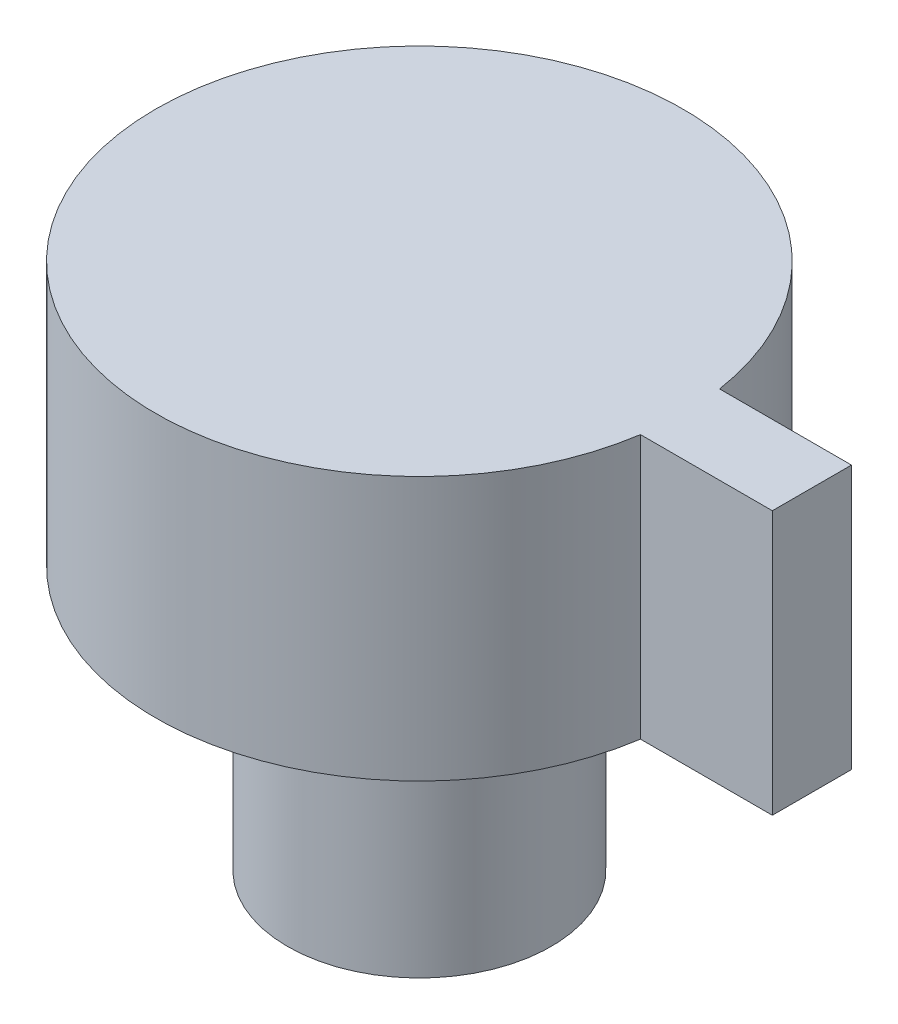
SolidWorks part; units mm, degrees
ref_plane "Front" through (0, 0, 0) normal (0, 0, 1) x (1, 0, 0)
ref_plane "Top" through (0, 0, 0) normal (0, 1, 0) x (1, 0, 0)
ref_plane "Right" through (0, 0, 0) normal (1, 0, 0) x (0, 0, -1)
sketch "Sketch1" plane through (0, 0, 0) normal (0, 1, 0) x (1, 0, 0)
  line L0 (-56.17, -16.2143) -> (-51.17, -16.2143)
  line L1 (-51.17, -16.2143) -> (-51.17, -19.2143)
  line L2 (-51.17, -19.2143) -> (-56.17, -19.2143)
  arc A0 (-56.17, -16.2143) -> (-56.17, -19.2143) centre (-66.0533, -17.7143) ccw
  arc A1 (-56.1664, -16.2143) -> (-56.1664, -19.2143) centre (-66.0533, -17.7143) ccw construction
  circle A2 centre (-66.0533, -17.7143) radius 5
  dimension "D1" = 9.9965
  dimension "D4" = 10
  dimension "D2" = 5
  dimension "D3" = 3
extrude "Boss-Extrude1" add sketch "Sketch1" along normal blind 10 contours L0 A0 L2 L1 A2 | A2 region at (-53.67, 0, 16.5335) region at (-66.0533, 0, 17.7143)
extrude "Boss-Extrude2" add sketch "Sketch1<3>" against normal blind 10 contours A2 region at (-66.0533, 0, 17.7143)
sketch "Sketch1<3>" plane through (0, 0, 0) normal (0, 1, 0) x (1, 0, 0) same geometry as "Sketch1"
